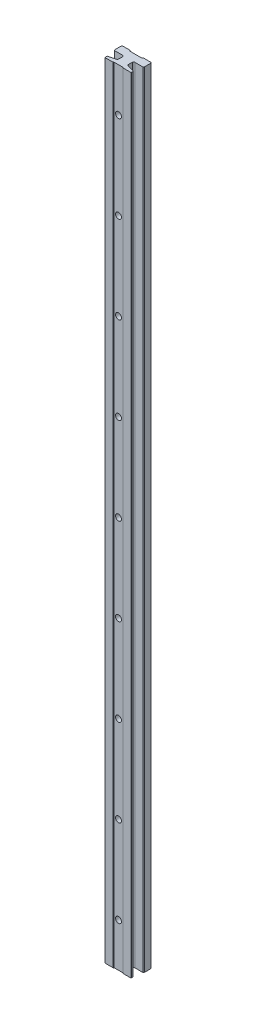
SolidWorks part; units mm, degrees
ref_plane "Front Plane" through (0, 0, 0) normal (0, 0, 1) x (1, 0, 0)
ref_plane "Top Plane" through (0, 0, 0) normal (0, 1, 0) x (1, 0, 0)
ref_plane "Right Plane" through (0, 0, 0) normal (1, 0, 0) x (0, 0, -1)
sketch "Sketch1" plane through (0, 0, 0) normal (0, 1, 0) x (1, 0, 0)
  line L0 (0, 0.2) -> (0, 1.15)
  line L1 (0.1482, 1.3432) -> (4.0088, 2.3776)
  line L2 (4.75, 3.3436) -> (4.75, 5.5)
  line L3 (4.05, 6.2) -> (-0.6, 6.2)
  line L4 (-1, 6.6) -> (-1, 10.4)
  line L5 (-0.6, 10.8) -> (3.5, 10.8)
  line L6 (3.5, 10.8) -> (4, 10.3)
  line L7 (-0.6, 6.2) -> (-1, 6.6)
  line L8 (-1, 10.4) -> (-0.6, 10.8)
  line L9 (4, 10.3) -> (11, 10.3)
  line L10 (7.5, 0.3) -> (7.5, 10.3) construction
  line L11 (10.25, 0) -> (9.95, 0.3)
  line L12 (10.25, 0) -> (14.8, 0)
  line L13 (15, 0.2) -> (15, 1.15)
  line L14 (14.8518, 1.3432) -> (10.9912, 2.3776)
  line L15 (10.25, 3.3436) -> (10.25, 5.5)
  line L16 (4.75, 0) -> (5.05, 0.3)
  line L17 (5.05, 0.3) -> (9.95, 0.3)
  line L18 (10.95, 6.2) -> (15.6, 6.2)
  line L19 (4.75, 0) -> (0.2, 0)
  line L20 (15.6, 6.2) -> (16, 6.6)
  line L21 (16, 6.6) -> (16, 10.4)
  line L22 (16, 10.4) -> (15.6, 10.8)
  line L23 (15.6, 10.8) -> (11.5, 10.8)
  line L24 (11.5, 10.8) -> (11, 10.3)
  arc A0 (15, 0.2) -> (14.8, 0) centre (14.8, 0.2) cw
  arc A1 (14.8518, 1.3432) -> (15, 1.15) centre (14.8, 1.15) cw
  arc A2 (0.1482, 1.3432) -> (0, 1.15) centre (0.2, 1.15) ccw
  arc A3 (0, 0.2) -> (0.2, 0) centre (0.2, 0.2) ccw
  arc A4 (4.75, 5.5) -> (4.05, 6.2) centre (4.05, 5.5) ccw
  arc A5 (4.75, 3.3436) -> (4.0088, 2.3776) centre (3.75, 3.3436) cw
  arc A6 (10.25, 3.3436) -> (10.9912, 2.3776) centre (11.25, 3.3436) ccw
  arc A7 (10.25, 5.5) -> (10.95, 6.2) centre (10.95, 5.5) cw
  point P31 (0, 0)
  point P33 (7.7857, 2.5762)
  point P36 (4.75, 2.5762)
  dimension "D3" = 0.3
  dimension "D8" = 0.4
  dimension "D11" = 1
  dimension "D12" = 0.7
  dimension "D5" = 0.2
  dimension "D2" = 4.9
  dimension "D4" = 4.55
  dimension "D6" = 0.3
  dimension "D7" = 3.8
  dimension "D9" = 0.95
  dimension "D10" = 1
  dimension "D13" = 15
  dimension "D14" = 4.75
  dimension "D15" = 6.2
  dimension "D20" = 0.4
  dimension "D19" = 0.4
  dimension "D16" = 0.5
  dimension "D17" = 0.5
  dimension "D21" = 7
  dimension "D18" = 0.4
extrude "Boss-Extrude1" add sketch "Sketch1" along normal blind 50 contours L19 A3 L0 A2 L1 A5 L2 A4 L3 L7 L4 L8 L5 L6 L9 L24 L23 L22 L21 L20 L18 A7 L15 A6 L14 A1 L13 A0 L12 L11 L17 L16
sketch "Sketch2" plane through (0, 0, 0) normal (0, 0, 1) x (1, 0, 0)
  line L0 (7.5, 25) -> (14.8, 25) construction
  line L1 (14.8, 50) -> (14.8, 0) construction
  line L2 (7.5, 25) -> (7.5, 0) construction
  line L3 (5.05, 0) -> (9.95, 0) construction
  circle A0 centre (7.5, 25) radius 1.7
  dimension "D1" = 3.4
extrude "Cut-Extrude1" cut sketch "Sketch2" against normal through all
sketch "Sketch3" plane through (0, 0, -10.3) normal (0, 0, -1) x (-1, 0, 0)
  circle A0 centre (-7.5, 25) radius 3
  dimension "D1" = 6
extrude "Cut-Extrude2" cut sketch "Sketch3" against normal blind 3.2 contours A0
pattern_linear "LPattern1" count 9 spacing 50 along (0, -1, 0) of "Boss-Extrude1", "Cut-Extrude1", "Cut-Extrude2"
